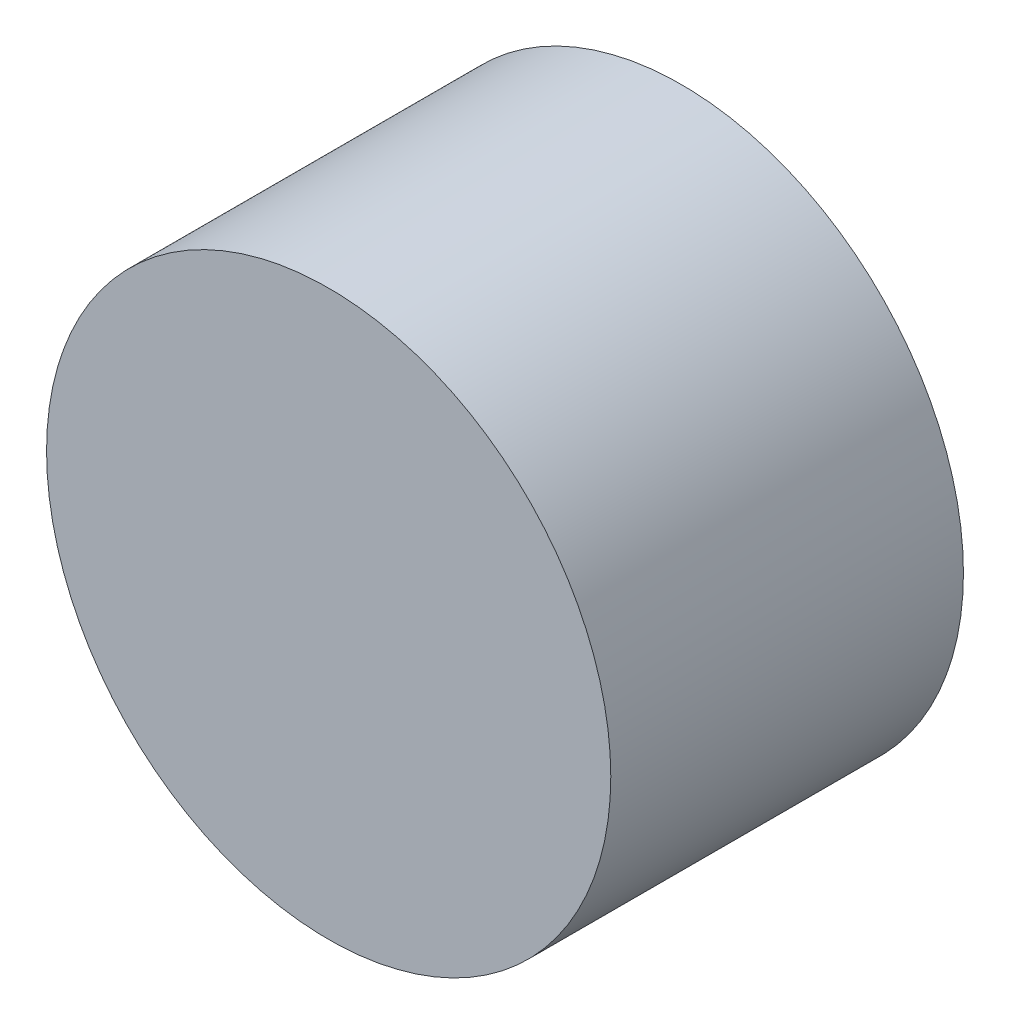
SolidWorks part; units mm, degrees
ref_plane "前视基准面" through (0, 0, 0) normal (0, 0, 1) x (1, 0, 0)
ref_plane "上视基准面" through (0, 0, 0) normal (0, 1, 0) x (1, 0, 0)
ref_plane "右视基准面" through (0, 0, 0) normal (1, 0, 0) x (0, 0, -1)
other "Configuration Table"
sketch "Sketch1" plane through (0, 0, 0) normal (0, 0, 1) x (1, 0, 0)
  circle A0 centre (0, 0) radius 40
extrude "Boss-Extrude1" add sketch "Sketch1" along normal blind 50
ref_plane "mount_face_bottom" through (0, 0, 0) normal (0, 0, 1) x (1, 0, 0)
ref_plane "mount_face_top" through (0, 0, 50) normal (0, 0, 1) x (1, 0, 0)
sketch3d "3DSketch1"
  line L0 (0, 0, 0) -> (0, 0, 50) construction
ref_axis "main_axis_z" through (0, 0, 0) along (0, 0, 1)
